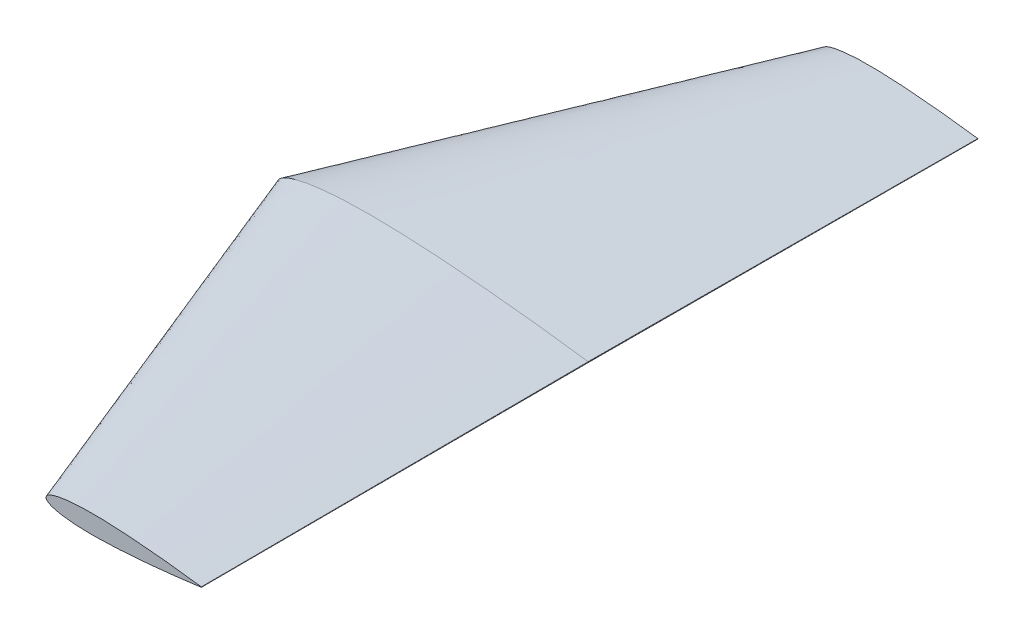
SolidWorks part; units mm, degrees
ref_plane "Front Plane" through (0, 0, 0) normal (0, 0, 1) x (1, 0, 0)
ref_plane "Top Plane" through (0, 0, 0) normal (0, 1, 0) x (1, 0, 0)
ref_plane "Right Plane" through (0, 0, 0) normal (1, 0, 0) x (0, 0, -1)
curve "Curve2"
  spline degree 3 poles (25.4, 0.032, 0) (25.3951, 0.0327, 0) (25.3753, 0.0355, 0) (25.3309, 0.0417, 0) (25.257, 0.052, 0) (25.1537, 0.0664, 0) (25.0214, 0.0846, 0) (24.8603, 0.1068, 0) (24.6708, 0.1326, 0) (24.4533, 0.1619, 0) (24.2084, 0.1946, 0) (23.9366, 0.2304, 0) (23.6385, 0.2691, 0) (23.3149, 0.3106, 0) (22.9666, 0.3545, 0) (22.5942, 0.4008, 0) (22.1987, 0.449, 0) (21.7811, 0.499, 0) (21.3422, 0.5505, 0) (20.8832, 0.6032, 0) (20.405, 0.6571, 0) (19.9089, 0.7116, 0) (19.3959, 0.7667, 0) (18.8673, 0.8219, 0) (18.3242, 0.8772, 0) (17.7681, 0.9321, 0) (17.2001, 0.9864, 0) (16.6216, 1.0399, 0) (16.0339, 1.0922, 0) (15.4384, 1.143, 0) (14.8366, 1.1921, 0) (14.2297, 1.2391, 0) (13.6193, 1.2836, 0) (13.0067, 1.3254, 0) (12.3935, 1.3642, 0) (11.7809, 1.3995, 0) (11.1705, 1.4311, 0) (10.5636, 1.4587, 0) (9.9618, 1.4818, 0) (9.3663, 1.5004, 0) (8.7786, 1.514, 0) (8.2001, 1.5224, 0) (7.632, 1.5254, 0) (7.0758, 1.5227, 0) (6.5327, 1.5144, 0) (6.0041, 1.5, 0) (5.491, 1.4798, 0) (4.9948, 1.4535, 0) (4.5166, 1.4212, 0) (4.0575, 1.3829, 0) (3.6185, 1.3388, 0) (3.2008, 1.2888, 0) (2.8052, 1.2334, 0) (2.4327, 1.1725, 0) (2.0841, 1.1064, 0) (1.7603, 1.0355, 0) (1.462, 0.96, 0) (1.1898, 0.8801, 0) (0.9445, 0.7962, 0) (0.7264, 0.7086, 0) (0.536, 0.6175, 0) (0.3737, 0.523, 0) (0.2396, 0.4254, 0) (0.1341, 0.3245, 0) (0.0574, 0.22, 0) (0.0105, 0.1114, 0) (-0.0051, 0, 0) (0.0105, -0.1114, 0) (0.0574, -0.22, 0) (0.1341, -0.3245, 0) (0.2396, -0.4254, 0) (0.3737, -0.523, 0) (0.536, -0.6175, 0) (0.7264, -0.7086, 0) (0.9445, -0.7962, 0) (1.1898, -0.8801, 0) (1.462, -0.96, 0) (1.7603, -1.0355, 0) (2.0841, -1.1064, 0) (2.4327, -1.1725, 0) (2.8052, -1.2334, 0) (3.2008, -1.2888, 0) (3.6185, -1.3388, 0) (4.0575, -1.3829, 0) (4.5166, -1.4212, 0) (4.9948, -1.4535, 0) (5.491, -1.4798, 0) (6.0041, -1.5, 0) (6.5327, -1.5144, 0) (7.0758, -1.5227, 0) (7.632, -1.5254, 0) (8.2001, -1.5224, 0) (8.7786, -1.514, 0) (9.3663, -1.5004, 0) (9.9618, -1.4818, 0) (10.5636, -1.4587, 0) (11.1705, -1.4311, 0) (11.7809, -1.3995, 0) (12.3935, -1.3642, 0) (13.0067, -1.3254, 0) (13.6193, -1.2836, 0) (14.2297, -1.2391, 0) (14.8366, -1.1921, 0) (15.4384, -1.143, 0) (16.0339, -1.0922, 0) (16.6216, -1.0399, 0) (17.2001, -0.9864, 0) (17.7681, -0.9321, 0) (18.3242, -0.8772, 0) (18.8673, -0.8219, 0) (19.3959, -0.7667, 0) (19.9089, -0.7116, 0) (20.405, -0.6571, 0) (20.8832, -0.6032, 0) (21.3422, -0.5505, 0) (21.7811, -0.499, 0) (22.1987, -0.449, 0) (22.5942, -0.4008, 0) (22.9666, -0.3545, 0) (23.3149, -0.3106, 0) (23.6385, -0.2691, 0) (23.9366, -0.2304, 0) (24.2084, -0.1946, 0) (24.4533, -0.1619, 0) (24.6708, -0.1326, 0) (24.8603, -0.1068, 0) (25.0214, -0.0846, 0) (25.1537, -0.0664, 0) (25.257, -0.052, 0) (25.3309, -0.0417, 0) (25.3753, -0.0355, 0) (25.3951, -0.0327, 0) (25.4, -0.032, 0) knots 0 0 0 0 0.000289 0.001156 0.002598 0.004612 0.007194 0.010336 0.014031 0.018272 0.023046 0.028343 0.03415 0.040454 0.047238 0.054489 0.062187 0.070314 0.078852 0.08778 0.097078 0.106722 0.116691 0.126961 0.137507 0.148306 0.159331 0.170556 0.181957 0.193504 0.205171 0.216932 0.228758 0.240621 0.252495 0.26435 0.276161 0.287898 0.299536 0.311047 0.322405 0.333584 0.344559 0.355306 0.3658 0.376018 0.385937 0.395538 0.404798 0.413699 0.422221 0.430349 0.438066 0.445357 0.452209 0.458612 0.464554 0.47003 0.475035 0.479569 0.483637 0.48725 0.490431 0.493219 0.495674 0.497891 0.5 0.502109 0.504326 0.506781 0.509569 0.51275 0.516363 0.520431 0.524965 0.52997 0.535446 0.541388 0.547791 0.554643 0.561934 0.569651 0.577779 0.586301 0.595202 0.604462 0.614063 0.623982 0.6342 0.644694 0.655441 0.666416 0.677595 0.688953 0.700464 0.712102 0.723839 0.73565 0.747505 0.759379 0.771242 0.783068 0.794829 0.806496 0.818043 0.829444 0.840669 0.851694 0.862493 0.873039 0.883309 0.893278 0.902922 0.91222 0.921148 0.929686 0.937813 0.945511 0.952762 0.959546 0.96585 0.971657 0.976954 0.981728 0.985969 0.989664 0.992806 0.995388 0.997402 0.998844 0.999711 1 1 1 1
sketch "Sketch1" plane through (0, 0, 0) normal (0, 0, 1) x (1, 0, 0)
  arc A0 (80.0329, 0.1008) -> (80.0329, -0.1008) centre (80, 0) cw
  spline S1 degree 3 poles (80.0329, 0.1008) (80.0173, 0.103) (79.955, 0.1118) (79.7065, 0.1465) (79.3346, 0.1985) (78.8398, 0.2667) (78.3322, 0.3365) (77.7351, 0.4178) (77.0499, 0.5101) (76.2781, 0.6131) (75.4217, 0.7259) (74.4827, 0.8481) (73.4631, 0.9786) (71.9499, 1.1696) (70.3376, 1.3678) (68.6301, 1.5722) (67.2473, 1.7345) (65.8008, 1.9007) (64.2942, 2.0703) (62.7309, 2.2421) (61.1145, 2.4157) (59.4489, 2.5897) (57.7378, 2.7639) (55.9854, 2.9369) (54.1957, 3.1082) (52.3729, 3.2766) (50.5212, 3.4415) (48.645, 3.6016) (46.7486, 3.7562) (44.8364, 3.9042) (42.9131, 4.0446) (40.9829, 4.1763) (39.0506, 4.2984) (36.483, 4.4465) (33.9269, 4.5714) (30.7711, 4.6929) (28.2866, 4.7613) (25.8376, 4.7969) (24.0477, 4.8063) (22.2952, 4.798) (20.584, 4.7717) (18.9183, 4.7265) (17.3017, 4.6627) (15.7382, 4.5798) (14.2314, 4.4781) (12.7847, 4.3575) (11.4016, 4.2183) (10.0853, 4.061) (8.8389, 3.8862) (7.6651, 3.6944) (6.5669, 3.4863) (5.5466, 3.2629) (4.6066, 3.0248) (3.7491, 2.7732) (2.9759, 2.5089) (2.2887, 2.2327) (1.6888, 1.9455) (1.1774, 1.6479) (0.755, 1.3404) (0.4226, 1.0225) (0.1808, 0.6933) (0.033, 0.3511) (-0.0161, 0) (0.033, -0.3511) (0.1808, -0.6933) (0.4226, -1.0225) (0.755, -1.3404) (1.1774, -1.6479) (1.6888, -1.9455) (2.2887, -2.2327) (2.9759, -2.5089) (3.7491, -2.7732) (4.6066, -3.0248) (5.5466, -3.2629) (6.5669, -3.4863) (7.6651, -3.6944) (8.8389, -3.8862) (10.0853, -4.061) (11.4016, -4.2183) (12.7847, -4.3575) (14.2314, -4.4781) (15.7382, -4.5798) (17.3017, -4.6627) (18.9183, -4.7265) (20.584, -4.7717) (22.2952, -4.798) (24.0477, -4.8063) (25.8376, -4.7969) (28.2866, -4.7613) (31.4094, -4.6753) (34.5648, -4.542) (37.1204, -4.4097) (39.0506, -4.2984) (40.9829, -4.1763) (42.9131, -4.0446) (44.8364, -3.9042) (46.7486, -3.7562) (48.645, -3.6016) (50.5212, -3.4415) (52.3729, -3.2766) (54.1957, -3.1082) (55.9854, -2.9369) (57.7378, -2.7639) (59.4489, -2.5897) (61.1145, -2.4157) (62.7309, -2.2421) (64.2942, -2.0703) (65.8008, -1.9007) (67.2473, -1.7345) (68.6301, -1.5722) (70.3376, -1.3678) (71.9499, -1.1696) (73.4631, -0.9786) (74.4827, -0.8481) (75.4217, -0.7259) (76.2781, -0.6131) (77.0499, -0.5101) (77.7351, -0.4178) (78.3322, -0.3365) (78.8398, -0.2667) (79.3346, -0.1985) (79.7065, -0.1465) (79.955, -0.1118) (80.0173, -0.103) (80.0329, -0.1008) knots 0 0 0 0 0.000289 0.001156 0.004612 0.007194 0.010336 0.014031 0.018272 0.023046 0.028343 0.03415 0.040454 0.047238 0.062187 0.070314 0.078852 0.08778 0.097078 0.106722 0.116691 0.126961 0.137507 0.148306 0.159331 0.170556 0.181957 0.193504 0.205171 0.216932 0.228758 0.240621 0.252495 0.26435 0.287898 0.299536 0.322405 0.333584 0.344559 0.355306 0.3658 0.376018 0.385937 0.395538 0.404798 0.413699 0.422221 0.430349 0.438066 0.445357 0.452209 0.458612 0.464554 0.47003 0.475035 0.479569 0.483637 0.48725 0.490431 0.493219 0.495674 0.497891 0.5 0.502109 0.504326 0.506781 0.509569 0.51275 0.516363 0.520431 0.524965 0.52997 0.535446 0.541388 0.547791 0.554643 0.561934 0.569651 0.577779 0.586301 0.595202 0.604462 0.614063 0.623982 0.6342 0.644694 0.655441 0.666416 0.677595 0.700464 0.723839 0.73565 0.747505 0.759379 0.771242 0.783068 0.794829 0.806496 0.818043 0.829444 0.840669 0.851694 0.862493 0.873039 0.883309 0.893278 0.902922 0.91222 0.921148 0.929686 0.937813 0.952762 0.959546 0.96585 0.971657 0.976954 0.981728 0.985969 0.989664 0.992806 0.995388 0.998844 0.999711 1 1 1 1
ref_plane "Plane1" through (0, 0, 100) normal (0, 0, 1) x (1, 0, 0)
sketch "Sketch2" plane through (0, 0, 100) normal (0, 0, 1) x (1, 0, 0)
  arc A0 (80.4, 0.0504) -> (80.4, -0.0504) centre (80.4, 0) cw
  spline S1 degree 3 poles (80.4, 0.0504) (80.3922, 0.0515) (80.3611, 0.0559) (80.2369, 0.0732) (80.051, 0.0992) (79.8037, 0.1333) (79.55, 0.1682) (79.2516, 0.2088) (78.9091, 0.255) (78.5234, 0.3064) (78.0954, 0.3628) (77.626, 0.4239) (77.1164, 0.4891) (76.3602, 0.5845) (75.5544, 0.6836) (74.7009, 0.7858) (74.0098, 0.8669) (73.2869, 0.95) (72.5339, 1.0347) (71.7526, 1.1206) (70.9447, 1.2073) (70.1122, 1.2943) (69.2571, 1.3814) (68.3812, 1.4678) (67.4867, 1.5534) (66.5757, 1.6376) (65.6502, 1.72) (64.7125, 1.8001) (63.7647, 1.8773) (62.809, 1.9513) (61.8477, 2.0215) (60.8831, 2.0873) (59.9173, 2.1483) (58.634, 2.2223) (57.3565, 2.2847) (55.7792, 2.3455) (54.5375, 2.3797) (53.3135, 2.3975) (52.4189, 2.4022) (51.543, 2.398) (50.6878, 2.3848) (49.8552, 2.3623) (49.0473, 2.3304) (48.2659, 2.289) (47.5128, 2.2381) (46.7897, 2.1778) (46.0985, 2.1083) (45.4406, 2.0297) (44.8176, 1.9423) (44.231, 1.8464) (43.6821, 1.7424) (43.1721, 1.6308) (42.7024, 1.5118) (42.2738, 1.386) (41.8873, 1.2539) (41.5439, 1.1159) (41.244, 0.9724) (40.9884, 0.8236) (40.7774, 0.6699) (40.6112, 0.511) (40.4904, 0.3465) (40.4165, 0.1755) (40.392, 0) (40.4165, -0.1755) (40.4904, -0.3465) (40.6112, -0.511) (40.7774, -0.6699) (40.9884, -0.8236) (41.244, -0.9724) (41.5439, -1.1159) (41.8873, -1.2539) (42.2738, -1.386) (42.7024, -1.5118) (43.1721, -1.6308) (43.6821, -1.7424) (44.231, -1.8464) (44.8176, -1.9423) (45.4406, -2.0297) (46.0985, -2.1083) (46.7897, -2.1778) (47.5128, -2.2381) (48.2659, -2.289) (49.0473, -2.3304) (49.8552, -2.3623) (50.6878, -2.3848) (51.543, -2.398) (52.4189, -2.4022) (53.3135, -2.3975) (54.5375, -2.3797) (56.0982, -2.3367) (57.6753, -2.2701) (58.9526, -2.204) (59.9173, -2.1483) (60.8831, -2.0873) (61.8477, -2.0215) (62.809, -1.9513) (63.7647, -1.8773) (64.7125, -1.8001) (65.6502, -1.72) (66.5757, -1.6376) (67.4867, -1.5534) (68.3812, -1.4678) (69.2571, -1.3814) (70.1122, -1.2943) (70.9447, -1.2073) (71.7526, -1.1206) (72.5339, -1.0347) (73.2869, -0.95) (74.0098, -0.8669) (74.7009, -0.7858) (75.5544, -0.6836) (76.3602, -0.5845) (77.1164, -0.4891) (77.626, -0.4239) (78.0954, -0.3628) (78.5234, -0.3064) (78.9091, -0.255) (79.2516, -0.2088) (79.55, -0.1682) (79.8037, -0.1333) (80.051, -0.0992) (80.2369, -0.0732) (80.3611, -0.0559) (80.3922, -0.0515) (80.4, -0.0504) knots 0 0 0 0 0.000289 0.001156 0.004612 0.007194 0.010336 0.014031 0.018272 0.023046 0.028343 0.03415 0.040454 0.047238 0.062187 0.070314 0.078852 0.08778 0.097078 0.106722 0.116691 0.126961 0.137507 0.148306 0.159331 0.170556 0.181957 0.193504 0.205171 0.216932 0.228758 0.240621 0.252495 0.26435 0.287898 0.299536 0.322405 0.333584 0.344559 0.355306 0.3658 0.376018 0.385937 0.395538 0.404798 0.413699 0.422221 0.430349 0.438066 0.445357 0.452209 0.458612 0.464554 0.47003 0.475035 0.479569 0.483637 0.48725 0.490431 0.493219 0.495674 0.497891 0.5 0.502109 0.504326 0.506781 0.509569 0.51275 0.516363 0.520431 0.524965 0.52997 0.535446 0.541388 0.547791 0.554643 0.561934 0.569651 0.577779 0.586301 0.595202 0.604462 0.614063 0.623982 0.6342 0.644694 0.655441 0.666416 0.677595 0.700464 0.723839 0.73565 0.747505 0.759379 0.771242 0.783068 0.794829 0.806496 0.818043 0.829444 0.840669 0.851694 0.862493 0.873039 0.883309 0.893278 0.902922 0.91222 0.921148 0.929686 0.937813 0.952762 0.959546 0.96585 0.971657 0.976954 0.981728 0.985969 0.989664 0.992806 0.995388 0.998844 0.999711 1 1 1 1
  point P0 (40.4, 0)
  point P4 (40.4, 0)
  dimension "D1" = 40.4
loft "Loft1" add profiles "Sketch1", "Sketch2" connector at (80.0329, 0.1008, 0) connector at (80.4, 0.0504, 100)
mirror "Mirror1" about plane through (0, 0, 0) normal (0, 0, -1) of "Loft1"
